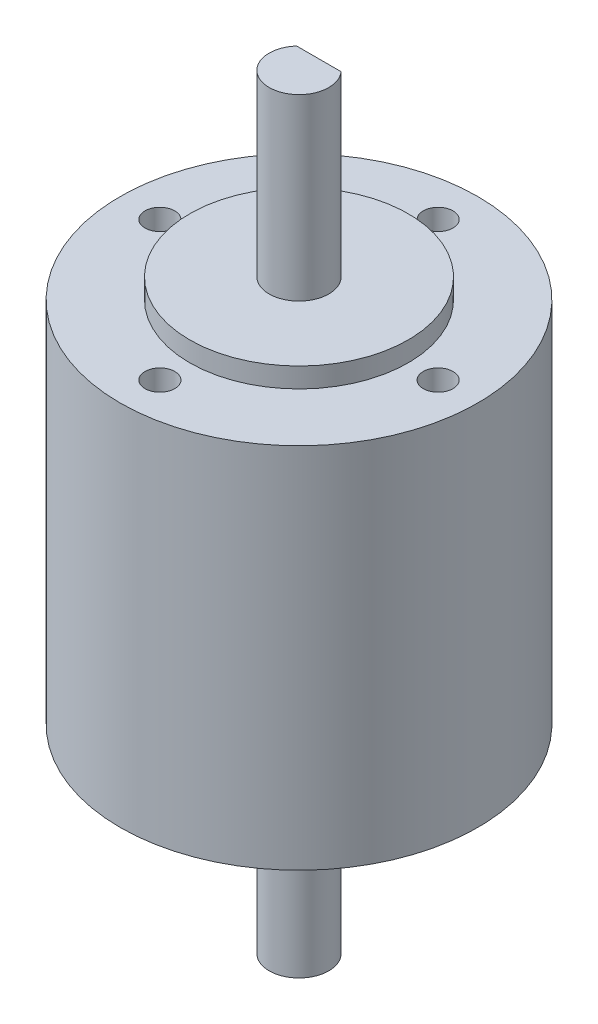
SolidWorks part; units mm, degrees
ref_plane "Front Plane" through (0, 0, 0) normal (0, 0, 1) x (1, 0, 0)
ref_plane "Top Plane" through (0, 0, 0) normal (0, 1, 0) x (1, 0, 0)
ref_plane "Right Plane" through (0, 0, 0) normal (1, 0, 0) x (0, 0, -1)
sketch "Sketch1" plane through (0, 0, 0) normal (0, 1, 0) x (1, 0, 0)
  circle A0 centre (0, 0) radius 18
  dimension "D1" = 36
extrude "Boss-Extrude1" add sketch "Sketch1" along normal mid plane 37
sketch "Sketch2" plane through (0, 18.5, 0) normal (0, 1, 0) x (1, 0, 0)
  circle A0 centre (0, 0) radius 11
  dimension "D1" = 22
extrude "Boss-Extrude2" add sketch "Sketch2" along normal blind 2
sketch "Sketch3" plane through (0, 20.5, 0) normal (0, 1, 0) x (1, 0, 0)
  circle A0 centre (0, 0) radius 3
  dimension "D1" = 6
extrude "Boss-Extrude4" add sketch "Sketch3" along normal blind 18
sketch "Sketch4" plane through (0, 38.5, 0) normal (0, 1, 0) x (1, 0, 0)
  line L0 (-2.2361, 2) -> (2.2361, 2)
  line L1 (0, -3) -> (0, 2) construction
  arc A0 (0, -3) -> (2.2361, 2) centre (0, 0) ccw construction
  circle A1 centre (0, 0) radius 3
  arc A2 (2.2361, 2) -> (-2.2361, 2) centre (0, 0) ccw
  arc A3 (-2.2361, 2) -> (0, -3) centre (0, 0) ccw construction
  dimension "D2" = 5
  dimension "D1" = 0
extrude "Cut-Extrude1" cut sketch "Sketch4" against normal blind 15
sketch "Sketch5" plane through (0, 18.5, 0) normal (0, 1, 0) x (1, 0, 0)
  circle A0 centre (0, 0) radius 14 construction
  circle A1 centre (0, 14) radius 1.5
  circle A2 centre (-14, 0) radius 1.5
  circle A3 centre (0, -14) radius 1.5
  circle A4 centre (14, 0) radius 1.5
  dimension "D1" = 28
  dimension "D2" = 3
extrude "Cut-Extrude2" cut sketch "Sketch5" against normal blind 4
mirror "Mirror1" about plane through (0, 0, 0) normal (0, 1, 0) of "Cut-Extrude2", "Cut-Extrude1", "Boss-Extrude4", "Boss-Extrude2"
